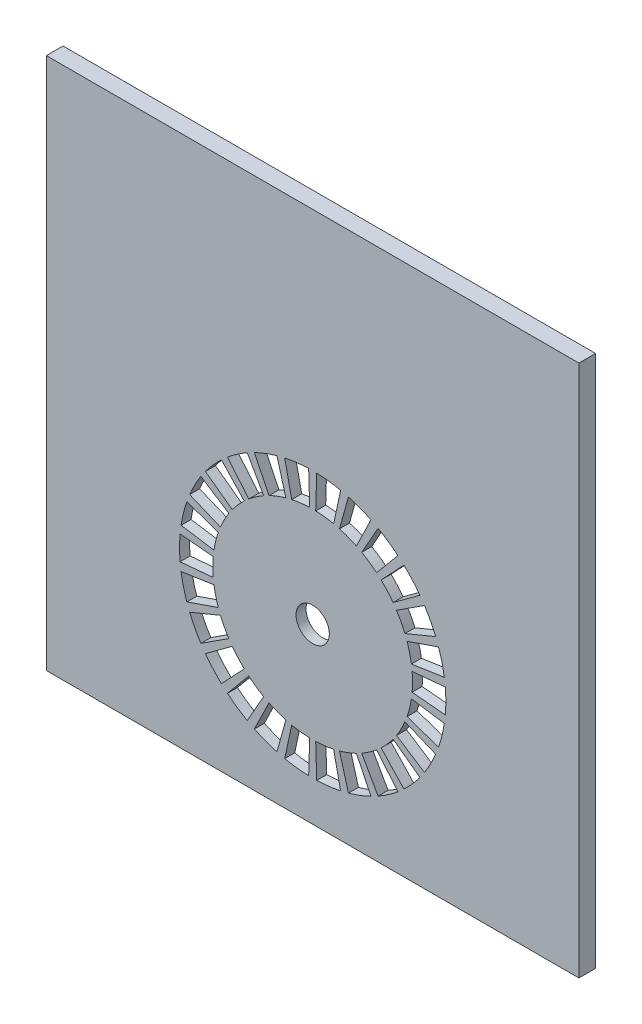
SolidWorks part; units mm, degrees
ref_plane "Front Plane" through (0, 0, 0) normal (0, 0, 1) x (1, 0, 0)
ref_plane "Top Plane" through (0, 0, 0) normal (0, 1, 0) x (1, 0, 0)
ref_plane "Right Plane" through (0, 0, 0) normal (1, 0, 0) x (0, 0, -1)
sketch "LED panel" plane through (0, 0, 0) normal (0, 0, 1) x (1, 0, 0)
  line L1 (-40, 40) -> (40, 40)
  line L2 (-40, 40) -> (-40, -40)
  line L3 (-40, -40) -> (40, -40)
  line L4 (40, 40) -> (40, -40)
  line L5 (-40, 40) -> (40, -40) construction
  line L6 (-40, -40) -> (40, 40) construction
  point P0 (0, 0)
  dimension "D1" = 80
  dimension "D2" = 80
extrude "Extrude LED panel" add sketch "LED panel" along normal blind 2.5
sketch "Sketch1" plane through (0, 0, 2.5) normal (0, 0, 1) x (1, 0, 0)
  line L0 (-40, -14) -> (40, -14) construction
  line L3 (0, 40) -> (0, -40) construction
  line L4 (40, 40) -> (-40, 40) construction
  line L5 (-40, -40) -> (40, -40) construction
  line L6 (0, -14) -> (52.2337, -7.6577) construction
  line L7 (0, -14) -> (47.0949, -19.7184) construction
  line L8 (0, -14) -> (19.9179, -12.19) construction
  line L9 (0, -14) -> (41.9979, -17.8164) construction
  line L10 (14.9384, -12.6425) -> (19.9179, -12.19)
  line L11 (14.9384, -15.3575) -> (19.9179, -15.81)
  line L12 (14.8292, -16.257) -> (19.7723, -17.0093)
  line L13 (14.1795, -18.893) -> (18.906, -20.5241)
  line L14 (13.8582, -19.7403) -> (18.4776, -21.6537)
  line L15 (12.5965, -22.1442) -> (16.7953, -24.859)
  line L16 (12.0818, -22.8899) -> (16.109, -25.8532)
  line L17 (10.2814, -24.9221) -> (13.7085, -28.5628)
  line L18 (9.6032, -25.523) -> (12.8043, -29.364)
  line L19 (7.3688, -27.0652) -> (9.8251, -31.4203)
  line L20 (6.5665, -27.4863) -> (8.7554, -31.9818)
  line L21 (4.028, -28.4491) -> (5.3706, -33.2654)
  line L22 (3.1482, -28.6659) -> (4.1976, -33.5545)
  line L23 (0.453, -28.9932) -> (0.6041, -33.9909)
  line L24 (-0.453, -28.9932) -> (-0.6041, -33.9909)
  line L25 (-3.1482, -28.6659) -> (-4.1976, -33.5545)
  line L26 (-4.028, -28.4491) -> (-5.3706, -33.2654)
  line L27 (-6.5665, -27.4863) -> (-8.7554, -31.9818)
  line L28 (-7.3688, -27.0652) -> (-9.8251, -31.4203)
  line L29 (-9.6032, -25.523) -> (-12.8043, -29.364)
  line L30 (-10.2814, -24.9221) -> (-13.7085, -28.5628)
  line L31 (-12.0818, -22.8899) -> (-16.109, -25.8532)
  line L32 (-12.5965, -22.1442) -> (-16.7953, -24.859)
  line L33 (-13.8582, -19.7403) -> (-18.4776, -21.6537)
  line L34 (-14.1795, -18.893) -> (-18.906, -20.5241)
  line L35 (-14.8292, -16.257) -> (-19.7723, -17.0093)
  line L36 (-14.9384, -15.3575) -> (-19.9179, -15.81)
  line L37 (-14.9384, -12.6425) -> (-19.9179, -12.19)
  line L38 (-14.8292, -11.743) -> (-19.7723, -10.9907)
  line L39 (-14.1795, -9.107) -> (-18.906, -7.4759)
  line L40 (-13.8582, -8.2597) -> (-18.4776, -6.3463)
  line L41 (-12.5965, -5.8558) -> (-16.7953, -3.141)
  line L42 (-12.0818, -5.1101) -> (-16.109, -2.1468)
  line L43 (-10.2814, -3.0779) -> (-13.7085, 0.5628)
  line L44 (-9.6032, -2.477) -> (-12.8043, 1.364)
  line L45 (-7.3688, -0.9348) -> (-9.8251, 3.4203)
  line L46 (-6.5665, -0.5137) -> (-8.7554, 3.9818)
  line L47 (-4.028, 0.4491) -> (-5.3706, 5.2654)
  line L48 (-3.1482, 0.6659) -> (-4.1976, 5.5545)
  line L49 (-0.453, 0.9932) -> (-0.6041, 5.9909)
  line L50 (0.453, 0.9932) -> (0.6041, 5.9909)
  line L51 (3.1482, 0.6659) -> (4.1976, 5.5545)
  line L52 (4.028, 0.4491) -> (5.3706, 5.2654)
  line L53 (6.5665, -0.5137) -> (8.7554, 3.9818)
  line L54 (7.3688, -0.9348) -> (9.8251, 3.4203)
  line L55 (9.6032, -2.477) -> (12.8043, 1.364)
  line L56 (10.2814, -3.0779) -> (13.7085, 0.5628)
  line L57 (12.0818, -5.1101) -> (16.109, -2.1468)
  line L58 (12.5965, -5.8558) -> (16.7953, -3.141)
  line L59 (13.8582, -8.2597) -> (18.4776, -6.3463)
  line L60 (14.1795, -9.107) -> (18.906, -7.4759)
  line L61 (14.8292, -11.743) -> (19.7723, -10.9907)
  line L62 (-40, -40) -> (40, -40) construction
  line L63 (40, -40) -> (40, 40) construction
  line L64 (-40, 40) -> (-40, -40) construction
  arc A0 (19.9179, -15.81) -> (19.9179, -12.19) centre (0, -14) ccw
  arc A1 (14.9384, -15.3575) -> (14.9384, -12.6425) centre (0, -14) ccw
  arc A2 (18.906, -20.5241) -> (19.7723, -17.0093) centre (0, -14) ccw
  arc A3 (14.1795, -18.893) -> (14.8292, -16.257) centre (0, -14) ccw
  arc A4 (16.7953, -24.859) -> (18.4776, -21.6537) centre (0, -14) ccw
  arc A5 (12.5965, -22.1442) -> (13.8582, -19.7403) centre (0, -14) ccw
  arc A6 (13.7085, -28.5628) -> (16.109, -25.8532) centre (0, -14) ccw
  arc A7 (10.2814, -24.9221) -> (12.0818, -22.8899) centre (0, -14) ccw
  arc A8 (9.8251, -31.4203) -> (12.8043, -29.364) centre (0, -14) ccw
  arc A9 (7.3688, -27.0652) -> (9.6032, -25.523) centre (0, -14) ccw
  arc A10 (5.3706, -33.2654) -> (8.7554, -31.9818) centre (0, -14) ccw
  arc A11 (4.028, -28.4491) -> (6.5665, -27.4863) centre (0, -14) ccw
  arc A12 (0.6041, -33.9909) -> (4.1976, -33.5545) centre (0, -14) ccw
  arc A13 (0.453, -28.9932) -> (3.1482, -28.6659) centre (0, -14) ccw
  arc A14 (-4.1976, -33.5545) -> (-0.6041, -33.9909) centre (0, -14) ccw
  arc A15 (-3.1482, -28.6659) -> (-0.453, -28.9932) centre (0, -14) ccw
  arc A16 (-8.7554, -31.9818) -> (-5.3706, -33.2654) centre (0, -14) ccw
  arc A17 (-6.5665, -27.4863) -> (-4.028, -28.4491) centre (0, -14) ccw
  arc A18 (-12.8043, -29.364) -> (-9.8251, -31.4203) centre (0, -14) ccw
  arc A19 (-9.6032, -25.523) -> (-7.3688, -27.0652) centre (0, -14) ccw
  arc A20 (-16.109, -25.8532) -> (-13.7085, -28.5628) centre (0, -14) ccw
  arc A21 (-12.0818, -22.8899) -> (-10.2814, -24.9221) centre (0, -14) ccw
  arc A22 (-18.4776, -21.6537) -> (-16.7953, -24.859) centre (0, -14) ccw
  arc A23 (-13.8582, -19.7403) -> (-12.5965, -22.1442) centre (0, -14) ccw
  arc A24 (-19.7723, -17.0093) -> (-18.906, -20.5241) centre (0, -14) ccw
  arc A25 (-14.8292, -16.257) -> (-14.1795, -18.893) centre (0, -14) ccw
  arc A26 (-19.9179, -12.19) -> (-19.9179, -15.81) centre (0, -14) ccw
  arc A27 (-14.9384, -12.6425) -> (-14.9384, -15.3575) centre (0, -14) ccw
  arc A28 (-18.906, -7.4759) -> (-19.7723, -10.9907) centre (0, -14) ccw
  arc A29 (-14.1795, -9.107) -> (-14.8292, -11.743) centre (0, -14) ccw
  arc A30 (-16.7953, -3.141) -> (-18.4776, -6.3463) centre (0, -14) ccw
  arc A31 (-12.5965, -5.8558) -> (-13.8582, -8.2597) centre (0, -14) ccw
  arc A32 (-13.7085, 0.5628) -> (-16.109, -2.1468) centre (0, -14) ccw
  arc A33 (-10.2814, -3.0779) -> (-12.0818, -5.1101) centre (0, -14) ccw
  arc A34 (-9.8251, 3.4203) -> (-12.8043, 1.364) centre (0, -14) ccw
  arc A35 (-7.3688, -0.9348) -> (-9.6032, -2.477) centre (0, -14) ccw
  arc A36 (-5.3706, 5.2654) -> (-8.7554, 3.9818) centre (0, -14) ccw
  arc A37 (-4.028, 0.4491) -> (-6.5665, -0.5137) centre (0, -14) ccw
  arc A38 (-0.6041, 5.9909) -> (-4.1976, 5.5545) centre (0, -14) ccw
  arc A39 (-0.453, 0.9932) -> (-3.1482, 0.6659) centre (0, -14) ccw
  arc A40 (4.1976, 5.5545) -> (0.6041, 5.9909) centre (0, -14) ccw
  arc A41 (3.1482, 0.6659) -> (0.453, 0.9932) centre (0, -14) ccw
  arc A42 (8.7554, 3.9818) -> (5.3706, 5.2654) centre (0, -14) ccw
  arc A43 (6.5665, -0.5137) -> (4.028, 0.4491) centre (0, -14) ccw
  arc A44 (12.8043, 1.364) -> (9.8251, 3.4203) centre (0, -14) ccw
  arc A45 (9.6032, -2.477) -> (7.3688, -0.9348) centre (0, -14) ccw
  arc A46 (16.109, -2.1468) -> (13.7085, 0.5628) centre (0, -14) ccw
  arc A47 (12.0818, -5.1101) -> (10.2814, -3.0779) centre (0, -14) ccw
  arc A48 (18.4776, -6.3463) -> (16.7953, -3.141) centre (0, -14) ccw
  arc A49 (13.8582, -8.2597) -> (12.5965, -5.8558) centre (0, -14) ccw
  arc A50 (19.7723, -10.9907) -> (18.906, -7.4759) centre (0, -14) ccw
  arc A51 (14.8292, -11.743) -> (14.1795, -9.107) centre (0, -14) ccw
  circle A52 centre (0, -14) radius 2.5
  point P124 (0, -14)
  dimension "D2" = 40
  dimension "D4" = 5
  dimension "D9" = 5
  dimension "D1" = 6.923
  dimension "D3" = 6.923
  dimension "D5" = 5.192
  dimension "D6" = 5.192
  dimension "D8" = 26
  dimension "D7" = 26
extrude "Cut arrow indication holes" cut sketch "Sketch1" against normal through all
sketch "Sketch2" plane through (0, 0, 0) normal (0, 0, -1) x (-1, 0, 0)
  line L0 (-1, 13.4818) -> (-1, 14.9818)
  line L1 (-1, 14.9818) -> (1, 14.9818)
  line L2 (1, 14.9818) -> (1, 13.4818)
  line L3 (0, -14) -> (0, 30.4199) construction
  line L4 (-8.9582, -40) -> (8.9582, -40)
  line L5 (40, -40) -> (-40, -40) construction
  arc A0 (-1, 13.4818) -> (-8.9582, -40) centre (0, -14) ccw
  arc A1 (8.9582, -40) -> (1, 13.4818) centre (0, -14) ccw
  point P5 (0, 14.9818)
  dimension "D1" = 55
  dimension "D2" = 2
  dimension "D3" = 1.5
extrude "Cut-Extrude2" cut sketch "Sketch2" against normal blind 1
equation "\"D6@Sketch1\"=3/4*360/2/26"
